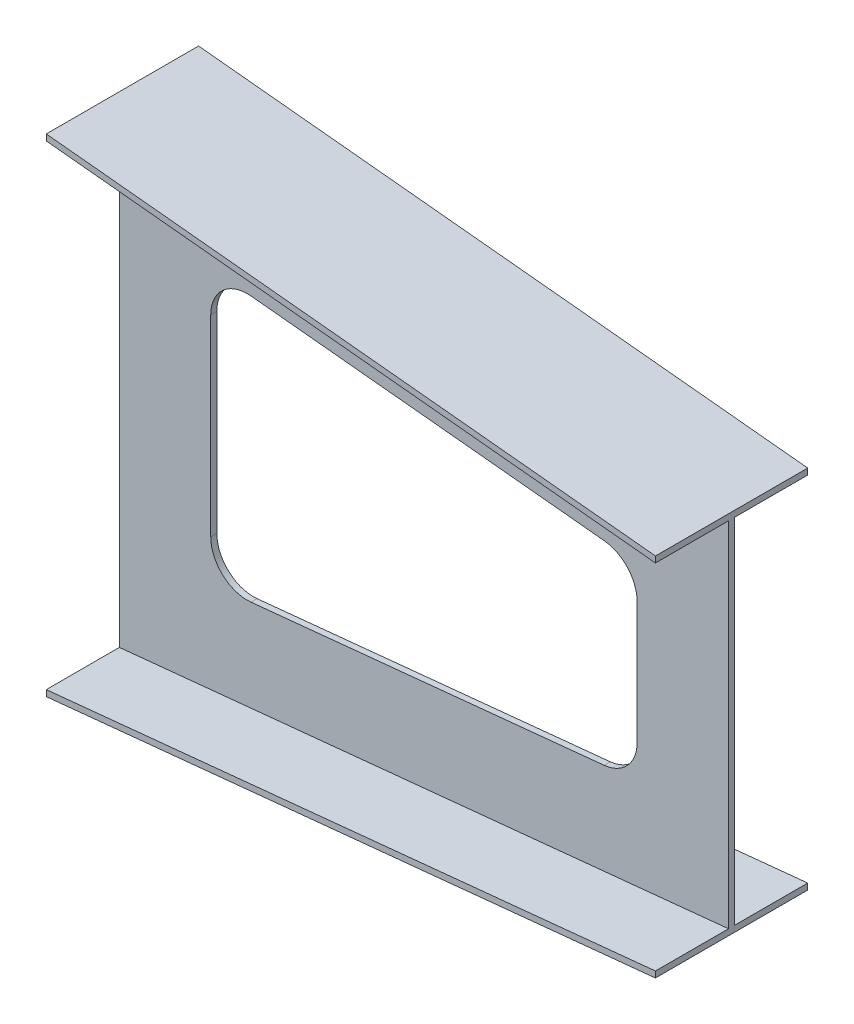
SolidWorks part; units mm, degrees
ref_plane "Front Plane" through (0, 0, 0) normal (0, 0, 1) x (1, 0, 0)
ref_plane "Top Plane" through (0, 0, 0) normal (0, 1, 0) x (1, 0, 0)
ref_plane "Right Plane" through (0, 0, 0) normal (1, 0, 0) x (0, 0, -1)
sketch "Sketch1" plane through (0, 0, 0) normal (1, 0, 0) x (0, 0, -1)
  line L1 (-130, 400) -> (120, 400)
  line L2 (-130, 400) -> (-130, 390)
  line L4 (120, 400) -> (120, 390)
  line L6 (-130, -390) -> (-130, -400)
  line L7 (-130, -400) -> (120, -400)
  line L8 (120, -390) -> (120, -400)
  line L15 (-130, -390) -> (-10, -390)
  line L16 (-5, 390) -> (-5, -590) construction
  line L18 (-130, 390) -> (-10, 390)
  line L19 (0, 0) -> (192.2403, 0) construction
  line L21 (-10, 390) -> (-10, -390)
  line L23 (0, 390) -> (0, -390)
  line L27 (0, 390) -> (120, 390)
  line L28 (0, -390) -> (120, -390)
  dimension "D1" = 250
  dimension "D2" = 10
  dimension "D3" = 800
  dimension "D4" = 10
ref_plane "Plane2" through (1000, 0, 0) normal (1, 0, 0) x (0, 0, -1)
sketch "Sketch4" plane through (1000, 0, -1000) normal (-1, 0, 0) x (0, 0, 1)
  line L1 (880, 300) -> (1130, 300)
  line L2 (880, 300) -> (880, 290)
  line L4 (1130, 300) -> (1130, 290)
  line L6 (880, -290) -> (880, -300)
  line L7 (880, -300) -> (1130, -300)
  line L8 (1130, -290) -> (1130, -300)
  line L15 (880, -290) -> (1000, -290)
  line L16 (1005, 390) -> (1005, -390) construction
  line L18 (880, 290) -> (1000, 290)
  line L19 (1010, -290) -> (1130, -290)
  line L21 (1000, 290) -> (1000, -290)
  line L23 (1010, 290) -> (1010, -290)
  line L24 (1010, 290) -> (1130, 290)
  line L26 (1010, 390) -> (1010, -390) construction
  line L27 (1000, 0) -> (820.2065, 0) construction
  dimension "D1" = 250
  dimension "D2" = 10
  dimension "D3" = 600
  dimension "D4" = 10
loft "Loft4" add profiles "Sketch1", "Sketch4" connector at (0, 390, 10) connector at (1000, 290, 10)
sketch "Sketch6" plane through (0, 0, 10) normal (0, 0, 1) x (1, 0, 0)
  line L8 (150, -224.2519) -> (850, -154.2519)
  line L9 (850, -154.2519) -> (850, 154.2519)
  line L10 (850, 154.2519) -> (150, 224.2519)
  line L11 (150, 224.2519) -> (150, -224.2519)
  line L12 (215.9702, -217.6548) -> (795.9702, -159.6548)
  line L13 (850, -99.9526) -> (850, 99.9526)
  line L14 (795.9702, 159.6548) -> (215.9702, 217.6548)
  line L15 (150, 157.9526) -> (150, -157.9526)
  arc A0 (150, -157.9526) -> (215.9702, -217.6548) centre (210, -157.9526) ccw
  arc A1 (850, 99.9526) -> (795.9702, 159.6548) centre (790, 99.9526) ccw
  arc A2 (850, -99.9526) -> (795.9702, -159.6548) centre (790, -99.9526) cw
  arc A3 (150, 157.9526) -> (215.9702, 217.6548) centre (210, 157.9526) cw
  dimension "D2" = 60
  dimension "D1" = 150
extrude "Cut-Extrude1" cut sketch "Sketch6" against normal blind 10
